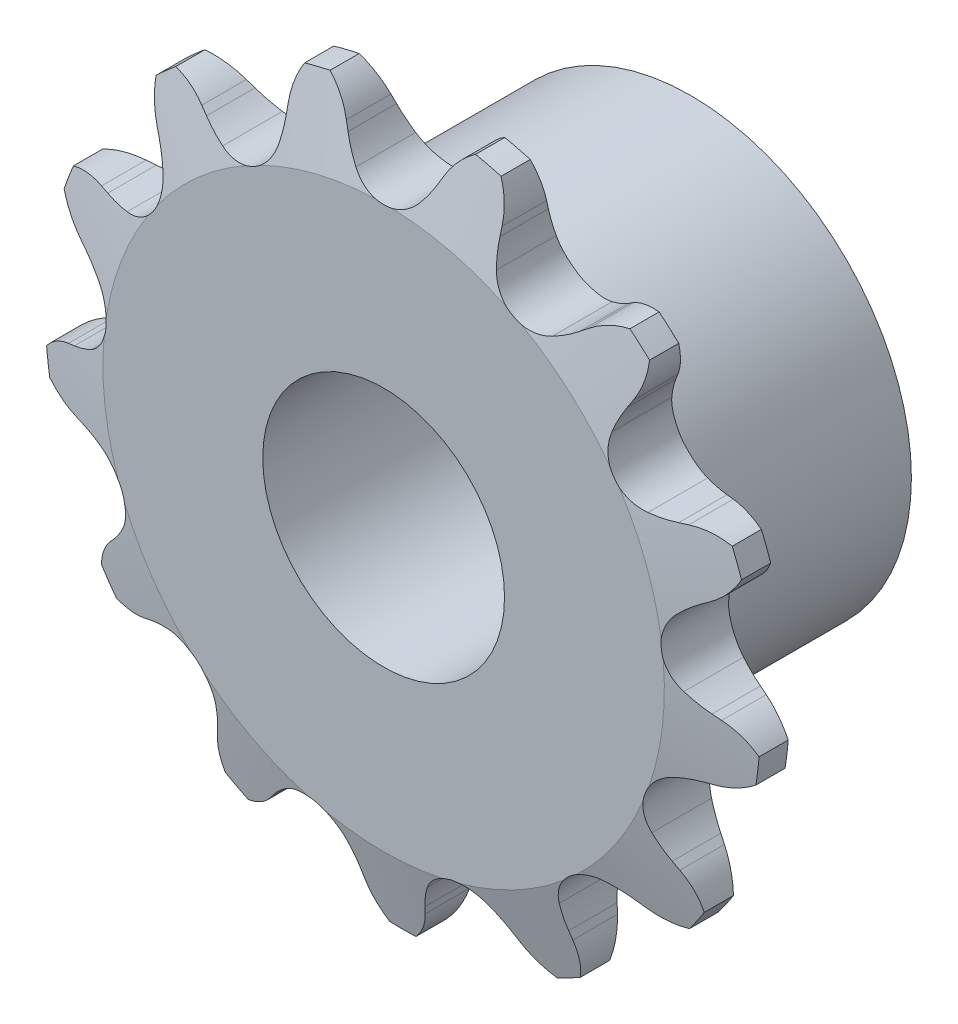
SolidWorks part; units mm, degrees
ref_plane "Front Plane" through (0, 0, 0) normal (0, 0, 1) x (1, 0, 0)
ref_plane "Top Plane" through (0, 0, 0) normal (0, 1, 0) x (1, 0, 0)
ref_plane "Right Plane" through (0, 0, 0) normal (1, 0, 0) x (0, 0, -1)
ref_axis "Axis1" through (0, 0, -88.99) along (0, 0, 1)
sketch "Sprocket-BaseSketch" plane through (0, 0, 0) normal (1, 0, 0) x (0, 0, -1)
  line L0 (1.397, 0) -> (1.397, 11.6115)
  line L1 (1.397, 11.6115) -> (0.6032, 14.7865)
  line L2 (0.6032, 14.7865) -> (-0.6032, 14.7865)
  line L3 (-0.6032, 14.7865) -> (-1.397, 11.6115)
  line L4 (-1.397, 11.6115) -> (-1.397, 0)
  line L5 (-1.397, 0) -> (1.397, 0)
  line L6 (5.588, 0) -> (-1.7463, 0) construction
  dimension "Hub Surface" = 1.397
  dimension "RightSide (1)" = 0.7938
  dimension "RightSide (2)" = 3.175
  dimension "OD" = 14.7865
  dimension "LeftSide (1)" = 0.7938
  dimension "LeftSide (2)" = 3.175
  dimension "Tooth Width" = 2.794
revolve "25 (04C) ANSI (ISO) Chain Number, 1.045in P.D." add sketch "Sprocket-BaseSketch" angle 360 about L6
sketch "Tooth-Sketch" plane through (0, 0, 0) normal (0, 0, 1) x (1, 0, 0)
  line L0 (0, 0) -> (0, 17.6893) construction
  line L1 (1.8674, 13.0545) -> (2.0169, 13.362)
  line L2 (-1.8674, 13.0545) -> (-2.0169, 13.362)
  line L3 (0, 13.267) -> (6.1655, 11.7473) construction
  line L4 (0, 13.267) -> (-6.1655, 11.7473) construction
  arc A0 (-1.3075, 12.1847) -> (1.3075, 12.1847) centre (0, 13.267) ccw
  arc A1 (1.3075, 12.1847) -> (1.8674, 13.0545) centre (-2.0349, 14.9514) ccw
  arc A2 (-1.3075, 12.1847) -> (-1.8674, 13.0545) centre (2.0349, 14.9514) cw
  arc A3 (2.0169, 13.362) -> (4.4885, 14.9087) centre (4.4885, 12.1607) cw
  arc A4 (-2.0169, 13.362) -> (-4.4885, 14.9087) centre (-4.4885, 12.1607) ccw
  arc A5 (4.4885, 14.9087) -> (-4.4885, 14.9087) centre (0, 0) ccw
extrude "Tooth-Cut, Number of teeth: 13" cut sketch "Tooth-Sketch" against normal through all and the other way through all
pattern_circular "Tooth Pattern, 13 / 13" count 13 every 27.692 about axis through (0, 0, -88.99) along (0, 0, 1) of "Tooth-Cut, Number of teeth: 13"
sketch "Sketch3" plane through (0, 0, 0) normal (1, 0, 0) x (0, 0, -1)
  line L0 (-9.906, 0) -> (9.906, 0) construction
  line L1 (1.397, 0) -> (1.397, 9.1288)
  line L2 (1.397, 9.1288) -> (11.303, 9.1288)
  line L3 (11.303, 9.1288) -> (11.303, 0)
  line L4 (11.303, 0) -> (1.397, 0)
  dimension "Hub Mounting" = 1.397
  dimension "Hub OD" = 9.1288
  dimension "Hub Width" = 9.906
revolve "Hub-Revolve1" add sketch "Sketch3" angle 360 about L0
sketch "Sketch4" plane through (0, 0, 0) normal (0, 0, 1) x (1, 0, 0)
  circle A0 centre (0, 0) radius 5
  dimension "D1" = 10
extrude "Cut-Extrude1" cut sketch "Sketch4" against normal through all and the other way through all
sketch "Sketch6" plane through (0, 0, 0) normal (0, 0, 1) x (1, 0, 0)
  circle A0 centre (0, 0) radius 14.7865
  dimension "D1" = 29.573
equation "\"D1@Sketch6\" = \"OD@Sprocket-BaseSketch\"*2"
